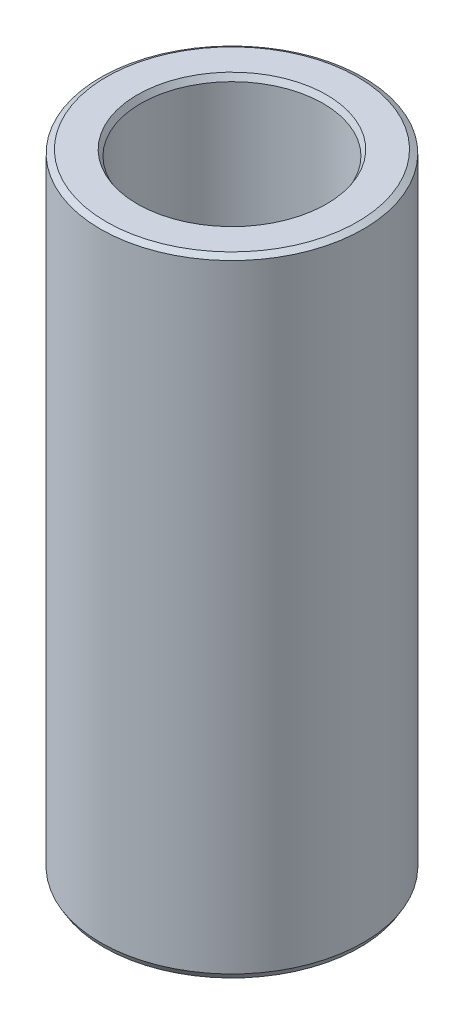
SolidWorks part; units mm, degrees
ref_plane "Front Plane" through (0, 0, 0) normal (0, 0, 1) x (1, 0, 0)
ref_plane "Top Plane" through (0, 0, 0) normal (0, 1, 0) x (1, 0, 0)
ref_plane "Right Plane" through (0, 0, 0) normal (1, 0, 0) x (0, 0, -1)
sketch "Sketch1" plane through (0, 0, 0) normal (0, 1, 0) x (1, 0, 0)
  circle A0 centre (0, 0) radius 47.5
  dimension "SLEEVE_OD" = 95
extrude "Boss-Extrude1" add sketch "Sketch1" along normal blind 226.6644
sketch "Sketch2" plane through (0, 0, 0) normal (0, 1, 0) x (1, 0, 0)
  circle A0 centre (0, 0) radius 32.9806
  dimension "BORE_D" = 65.9612
extrude "Cut-Extrude1" cut sketch "Sketch2" along normal through all
chamfer "Chamfer1" distance 1.2204 angle 60 4 edges at (0, 226.6644, 32.9806) (0, 0, 32.9806) (0, 0, 47.5) (0, 226.6644, 47.5) first distance on face at (0, 226.6644, 32.9806) first distance on face at (0, 0, 32.9806) first distance on face at (0, 226.6644, 47.5)
